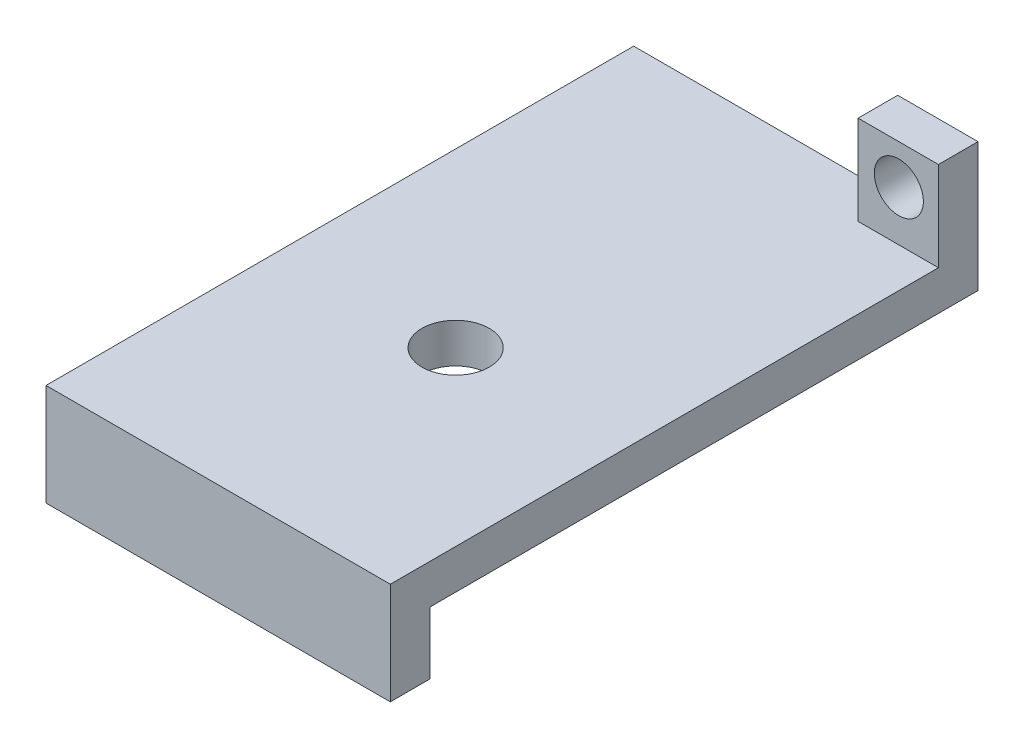
SolidWorks part; units mm, degrees
ref_plane "Front Plane" through (0, 0, 0) normal (0, 0, 1) x (1, 0, 0)
ref_plane "Top Plane" through (0, 0, 0) normal (0, 1, 0) x (1, 0, 0)
ref_plane "Right Plane" through (0, 0, 0) normal (1, 0, 0) x (0, 0, -1)
sketch "Sketch4" plane through (0, 0, 0) normal (0, 0, 1) x (1, 0, 0)
  line L1 (-11.049, 9.9695) -> (11.049, 9.9695)
  line L2 (-11.049, 9.9695) -> (-11.049, -9.9695)
  line L3 (-11.049, -9.9695) -> (11.049, -9.9695)
  line L4 (11.049, 9.9695) -> (11.049, -9.9695)
  line L5 (-11.049, 9.9695) -> (11.049, -9.9695) construction
  line L6 (-11.049, -9.9695) -> (11.049, 9.9695) construction
  circle A0 centre (-8.509, -5.5245) radius 1.5748
  circle A1 centre (8.509, 7.4295) radius 1.5748
  point P0 (0, 0)
  point P12 (11.049, 7.905)
  dimension "D4" = 3.1496
  dimension "D5" = 3.1496
  dimension "D6" = 17.018
  dimension "D8" = 2.54
  dimension "D1" = 19.939
  dimension "D2" = 22.098
  dimension "D3" = 15.494
  dimension "D7" = 2.54
sketch "Sketch5" plane through (0, 0, 0) normal (0, 0, 1) x (1, 0, 0)
  line L1 (1.4478, 1.0541) -> (9.3218, 1.0541)
  line L2 (1.4478, 1.0541) -> (1.4478, -6.6675)
  line L3 (1.4478, -6.6675) -> (9.3218, -6.6675)
  line L4 (9.3218, 1.0541) -> (9.3218, -6.6675)
  line L5 (-11.049, 9.9695) -> (11.049, 9.9695) construction
  line L8 (-11.049, 9.9695) -> (-11.049, -9.9695) construction
  dimension "D1" = 7.874
  dimension "D2" = 7.7216
  dimension "D3" = 8.9154
  dimension "D4" = 12.4968
sketch "Sketch6" plane through (0, 0, 0) normal (0, 0, 1) x (1, 0, 0)
  line L0 (11.049, 9.9695) -> (11.049, -9.9695) construction
  line L1 (11.049, 1.6891) -> (-6.0305, 1.6891)
  line L2 (11.049, 1.6891) -> (11.049, 4.2291)
  line L3 (5.8951, 4.2291) -> (-11.049, 4.2291)
  line L4 (-11.049, 1.6891) -> (-11.049, 4.2291)
  line L5 (-11.049, 9.9695) -> (-11.049, -9.9695) construction
  line L6 (1.4478, 1.0541) -> (9.3218, 1.0541) construction
  line L7 (-11.049, -9.9695) -> (11.049, -9.9695) construction
  line L9 (-11.049, 1.6891) -> (-11.049, -9.9695)
  line L10 (-11.049, -9.9695) -> (-6.0305, -9.9695)
  line L11 (-6.0305, 1.6891) -> (-6.0305, -9.9695)
  line L12 (-11.049, 9.9695) -> (11.049, 9.9695) construction
  line L14 (11.049, 4.2291) -> (11.049, 9.9695)
  line L15 (11.049, 9.9695) -> (5.8951, 9.9695)
  line L16 (5.8951, 4.2291) -> (5.8951, 9.9695)
  dimension "D1" = 0.635
  dimension "D2" = 2.54
extrude "Boss-Extrude1" add sketch "Sketch6" along normal blind 2.54
sketch "Sketch7" plane through (0, 0, 2.54) normal (0, 0, 1) x (1, 0, 0)
  line L1 (-11.049, 4.2291) -> (11.049, 4.2291)
  line L2 (-11.049, 4.2291) -> (-11.049, 1.6891)
  line L3 (-11.049, 1.6891) -> (11.049, 1.6891)
  line L4 (11.049, 4.2291) -> (11.049, 1.6891)
extrude "Boss-Extrude2" add sketch "Sketch7" along normal blind 32.639
sketch "Sketch8" plane through (0, 0, 2.54) normal (0, 0, 1) x (1, 0, 0)
  circle A0 centre (8.509, 7.4295) radius 1.5748
  circle A1 centre (-8.509, -5.5245) radius 1.5748
extrude "Cut-Extrude1" cut sketch "Sketch8" against normal through all
sketch "Sketch9" plane through (0, 4.2291, 0) normal (0, 1, 0) x (1, 0, 0)
  line L0 (11.049, -35.179) -> (-11.049, -35.179) construction
  circle A0 centre (0, -22.479) radius 2.16
  dimension "D1" = 12.7
  dimension "D2" = 4.32
extrude "Cut-Extrude2" cut sketch "Sketch9" against normal through all
sketch "Sketch10" plane through (0, 4.2291, 0) normal (0, 1, 0) x (1, 0, 0)
  line L1 (-11.049, -35.179) -> (11.049, -35.179)
  line L2 (-11.049, -35.179) -> (-11.049, -37.719)
  line L3 (-11.049, -37.719) -> (11.049, -37.719)
  line L4 (11.049, -35.179) -> (11.049, -37.719)
  dimension "D1" = 2.54
extrude "Boss-Extrude3" add sketch "Sketch10" against normal blind 6.54
